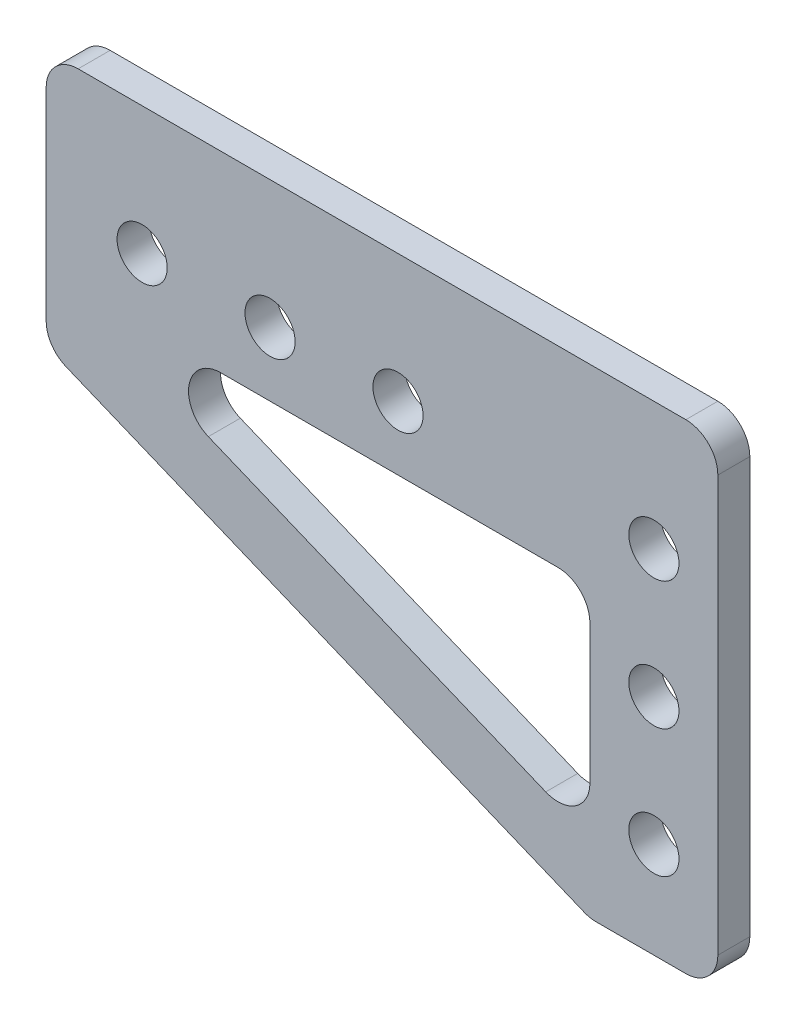
SolidWorks part; units mm, degrees
material "6061-T6 (SS)"
ref_plane "Front Plane" through (0, 0, 0) normal (0, 0, 1) x (1, 0, 0)
ref_plane "Top Plane" through (0, 0, 0) normal (0, 1, 0) x (1, 0, 0)
ref_plane "Right Plane" through (0, 0, 0) normal (1, 0, 0) x (0, 0, -1)
sketch "Sketch1" plane through (0, 0, 0) normal (0, 0, 1) x (1, 0, 0)
  line L7 (0, 0) -> (0, -25.4)
  line L8 (0, -25.4) -> (53.975, -47.625)
  line L9 (53.975, -47.625) -> (66.675, -47.625)
  line L10 (66.675, -47.625) -> (66.675, 0)
  line L11 (66.675, 0) -> (0, 0)
  line L12 (16.0968, -25.1609) -> (53.975, -40.7577)
  line L13 (53.975, -40.7577) -> (53.975, -19.05)
  line L14 (53.975, -19.05) -> (17.3057, -19.05)
  arc A12 (17.3057, -19.05) -> (16.0968, -25.1609) centre (17.3057, -22.225) ccw
  circle A18 centre (9.525, -12.7) radius 2.4892
  circle A19 centre (22.225, -12.7) radius 2.4892
  circle A20 centre (34.925, -12.7) radius 2.4892
  circle A22 centre (47.625, -12.7) radius 2.4892 [skipped]
  circle A23 centre (60.325, -12.7) radius 2.4892
  circle A24 centre (60.325, -25.4) radius 2.4892
  circle A25 centre (60.325, -38.1) radius 2.4892
  dimension "D5" = 12.7
  dimension "D6" = 9.525
  dimension "D8" = 12.7
  dimension "D10" = 12.7
  dimension "D2" = 4
  dimension "D1" = 4.9784
  dimension "D7" = 25.4
  dimension "D9" = 6.35
  dimension "D11" = 12.7
  dimension "D12" = 9.525
  dimension "D14" = 6.35
  dimension "D15" = 6.35
  dimension "D16" = 3.175
  dimension "D3" = 12.7
  dimension "D4" = 25.4
  dimension "D13" = 6.35
extrude "Boss-Extrude1" add sketch "Sketch1" along normal mid plane 3.175
fillet "Fillet1" radius 3.175 5 edges at (0, -25.4, 0) (0, 0, 0) (66.675, 0, 0) (66.675, -47.625, 0) (53.975, -47.625, 0)
fillet "Fillet2" radius 3.175 2 edges at (53.975, -19.05, 0) (53.975, -40.7577, 0)
